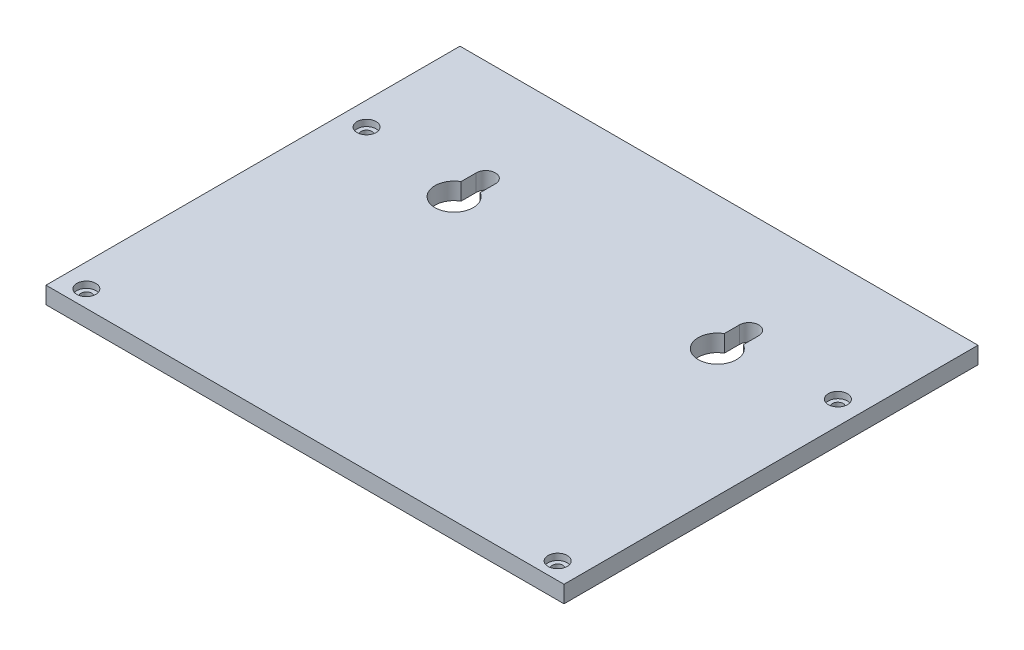
SolidWorks part; units mm, degrees
ref_plane "Front Plane" through (0, 0, 0) normal (0, 0, 1) x (1, 0, 0)
ref_plane "Top Plane" through (0, 0, 0) normal (0, 1, 0) x (1, 0, 0)
ref_plane "Right Plane" through (0, 0, 0) normal (1, 0, 0) x (0, 0, -1)
sketch "Sketch1" plane through (0, 0, 0) normal (0, 1, 0) x (1, 0, 0)
  line L1 (-91.4063, 40.0781) -> (30.5937, 40.0781)
  line L2 (-91.4063, 40.0781) -> (-91.4063, -57.4219)
  line L3 (-91.4063, -57.4219) -> (30.5938, -57.4219)
  line L4 (30.5937, 40.0781) -> (30.5938, -57.4219)
  dimension "D1" = 97.5
  dimension "D2" = 122
extrude "Boss-Extrude1" add sketch "Sketch1" along normal blind 4
sketch "Sketch2" plane through (0, 4, 0) normal (0, 1, 0) x (1, 0, 0)
  line L0 (-91.4063, 40.0781) -> (-91.4063, -57.4219) construction
  line L2 (-91.4063, -57.4219) -> (30.5938, -57.4219) construction
  line L3 (30.5938, -57.4219) -> (30.5937, 40.0781) construction
  circle A0 centre (-85.9063, -53.4219) radius 1.25
  circle A1 centre (-85.9063, 12.5781) radius 1.25
  circle A2 centre (25.0938, 12.5781) radius 1.25
  circle A3 centre (25.0937, -53.4219) radius 1.25
  dimension "D1" = 4
  dimension "D2" = 5.5
  dimension "D3" = 5.5
  dimension "D4" = 66
  dimension "D5" = 5.5
  dimension "D6" = 5.5
  dimension "D7" = 66
  dimension "D8" = 4
extrude "Cut-Extrude1" cut sketch "Sketch2" against normal blind 4
sketch "Sketch3" plane through (0, 4, 0) normal (0, 1, 0) x (1, 0, 0)
  circle A0 centre (-85.9063, 12.5781) radius 2.25
  circle A1 centre (-85.9063, -53.4219) radius 2.25
  circle A2 centre (25.0937, -53.4219) radius 2.25
  circle A3 centre (25.0938, 12.5781) radius 2.25
  dimension "D1" = 4.5
  dimension "D2" = 4.5
  dimension "D3" = 4.5
  dimension "D4" = 4.5
extrude "Cut-Extrude2" cut sketch "Sketch3" against normal blind 1.5
sketch "Sketch4" plane through (0, 4, 0) normal (0, 1, 0) x (1, 0, 0)
  line L3 (-1.6563, 16.1573) -> (-1.6563, 12.5863)
  line L4 (-63.6563, 16.1573) -> (-63.6563, 12.5863)
  line L6 (-59.1563, 16.1573) -> (-59.1563, 12.5863)
  line L7 (2.8437, 16.1573) -> (2.8437, 12.5863)
  arc A2 (-59.1563, 12.5863) -> (-63.6563, 12.5863) centre (-61.4063, 8.6896) cw
  arc A4 (-63.6563, 16.1573) -> (-59.1563, 16.1573) centre (-61.4063, 16.1573) cw
  arc A7 (-1.6563, 16.1573) -> (2.8437, 16.1573) centre (0.5937, 16.1573) cw
  arc A8 (2.8437, 12.5863) -> (-1.6563, 12.5863) centre (0.5937, 8.6896) cw
  dimension "D1" = 2
  dimension "D3" = 4.5
extrude "Cut-Extrude3" cut sketch "Sketch4" against normal blind 4
